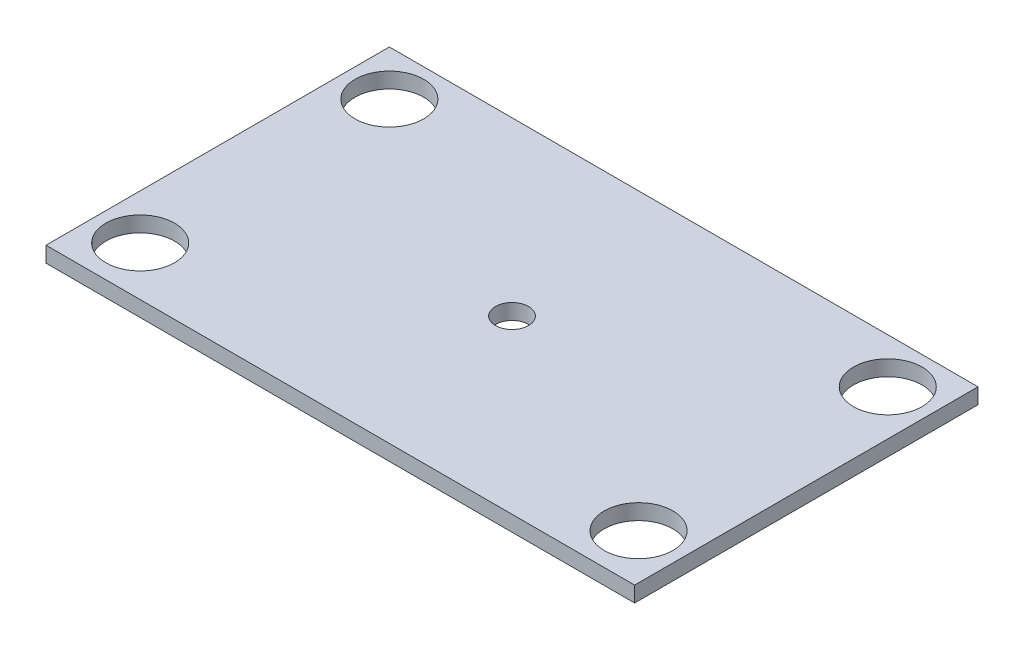
SolidWorks part; units mm, degrees
ref_plane "Front Plane" through (0, 0, 0) normal (0, 0, 1) x (1, 0, 0)
ref_plane "Top Plane" through (0, 0, 0) normal (0, 1, 0) x (1, 0, 0)
ref_plane "Right Plane" through (0, 0, 0) normal (1, 0, 0) x (0, 0, -1)
sketch "Sketch1" plane through (0, 0, 0) normal (0, 1, 0) x (1, 0, 0)
  line L0 (4.6, 30.4) -> (0, 30.4) construction
  line L1 (0, 0) -> (60, 0)
  line L2 (0, 0) -> (0, 35)
  line L3 (0, 35) -> (60, 35)
  line L4 (60, 0) -> (60, 35)
  line L5 (4.6, 30.4) -> (55.4, 30.4) construction
  line L6 (4.6, 30.4) -> (4.6, 5) construction
  line L7 (4.6, 5) -> (55.4, 5) construction
  line L8 (55.4, 30.4) -> (55.4, 5) construction
  line L9 (4.6, 30.4) -> (4.6, 35) construction
  circle A0 centre (4.6, 30.4) radius 3.5
  circle A1 centre (55.4, 30.4) radius 3.5
  circle A2 centre (4.6, 5) radius 3.5
  circle A3 centre (55.4, 5) radius 3.5
  circle A4 centre (30, 17.5) radius 1.6875
  point P13 (30, 30.4)
  point P14 (30, 35)
  point P20 (60, 17.5)
  dimension "D5" = 7
  dimension "D6" = 3.375
  dimension "D1" = 60
  dimension "D2" = 35
  dimension "D3" = 50.8
  dimension "D4" = 25.4
extrude "Boss-Extrude1" add sketch "Sketch1" along normal blind 1.5875
